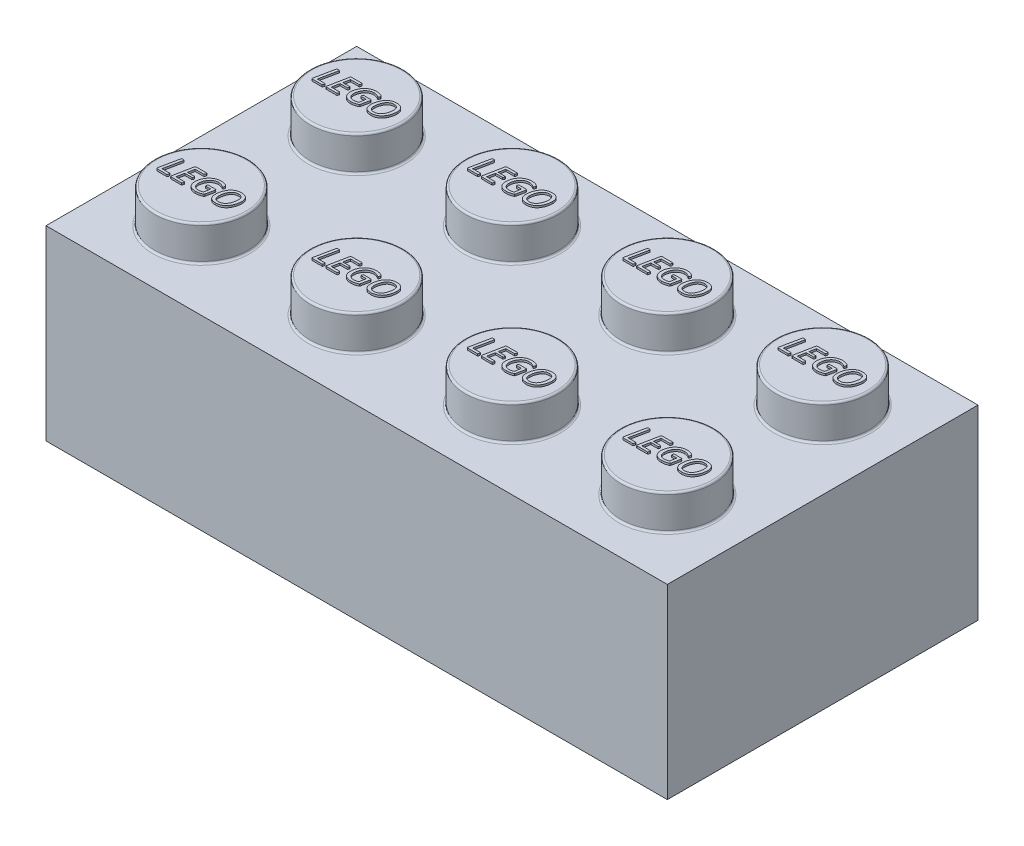
SolidWorks part; units mm, degrees
ref_plane "Front Plane" through (0, 0, 0) normal (0, 0, 1) x (1, 0, 0)
ref_plane "Top Plane" through (0, 0, 0) normal (0, 1, 0) x (1, 0, 0)
ref_plane "Right Plane" through (0, 0, 0) normal (1, 0, 0) x (0, 0, -1)
sketch "Sketch2" plane through (0, 0, 0) normal (0, 1, 0) x (1, 0, 0)
  line L1 (16, -8) -> (-16, -8)
  line L2 (16, -8) -> (16, 8)
  line L3 (16, 8) -> (-16, 8)
  line L4 (-16, -8) -> (-16, 8)
  line L5 (16, -8) -> (-16, 8) construction
  line L6 (16, 8) -> (-16, -8) construction
  point P0 (0, 0)
  dimension "D1" = 32
  dimension "D2" = 16
extrude "Boss-Extrude1" add sketch "Sketch2" along normal blind 9.6
sketch "Sketch3" plane through (0, 9.6, 0) normal (0, 1, 0) x (1, 0, 0)
  line L0 (-16, 8) -> (-16, 4) construction
  line L1 (-16, 8) -> (-16, -8) construction
  line L2 (-16, 4) -> (-12, 4) construction
  circle A0 centre (-12, 4) radius 2.4
  dimension "D3" = 4.8
  dimension "D1" = 4
  dimension "D2" = 4
extrude "Boss-Extrude2" add sketch "Sketch3" along normal blind 1.8
fillet "Fillet1" radius 0.1 2 edges at (-12, 11.4, -1.6) (-12, 9.6, -1.6)
sketch "Sketch4" plane through (0, 11.4, 0) normal (0, 1, 0) x (1, 0, 0)
  line L0 (-12, 6.3) -> (-12, 3.5) construction
  line L1 (-14.245, 3.5) -> (-9.755, 3.5) construction
  line L2 (-16, 8) -> (-16, -8) construction
  circle A0 centre (-12, 4) radius 2.3 construction
  text T0 "LEGO" font "Calibri" height in points 4
  point P9 (0, 0)
  dimension "D1" = 2.8
extrude "Boss-Extrude3" add sketch "Sketch4" along normal blind 0.1
pattern_linear "LPattern1" count 4 spacing 8 along (1, 0, 0) count 2 spacing 8 along (0, 0, 1) of "Boss-Extrude3", "Fillet1", "Boss-Extrude2"
